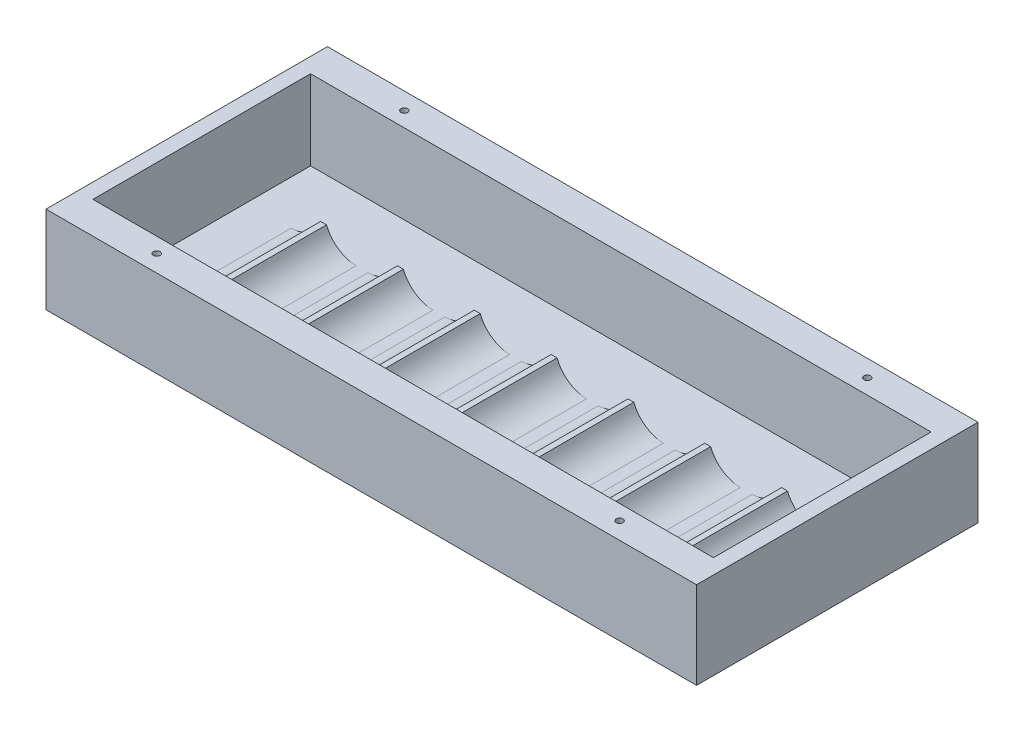
SolidWorks part; units mm, degrees
material "ABS"
ref_plane "Front Plane" through (0, 0, 0) normal (0, 0, 1) x (1, 0, 0)
ref_plane "Top Plane" through (0, 0, 0) normal (0, 1, 0) x (1, 0, 0)
ref_plane "Right Plane" through (0, 0, 0) normal (1, 0, 0) x (0, 0, -1)
sketch "Sketch1" plane through (0, 0, 0) normal (0, 1, 0) x (1, 0, 0)
  line L0 (5.08, -5.08) -> (5.08, -78.74)
  line L1 (0, 0) -> (220.16, 0)
  line L2 (0, 0) -> (0, -83.82)
  line L3 (0, -83.82) -> (220.16, -83.82)
  line L4 (220.16, 0) -> (220.16, -83.82)
  line L5 (5.08, -78.74) -> (215.08, -78.74)
  line L6 (215.08, -5.08) -> (215.08, -78.74)
  line L7 (5.08, -5.08) -> (215.08, -5.08)
  line L8 (0, 0) -> (0, 5.715)
  line L9 (0, 5.715) -> (220.16, 5.715)
  line L10 (220.16, 5.715) -> (220.16, 0)
  line L11 (0, -83.82) -> (0, -89.535)
  line L12 (0, -89.535) -> (220.16, -89.535)
  line L13 (220.16, -89.535) -> (220.16, -83.82)
  dimension "D1" = 73.66
  dimension "D2" = 210
  dimension "D4" = 10.795
  dimension "D5" = 95.25
  dimension "D3" = 5.08
extrude "Boss-Extrude1" add sketch "Sketch1" against normal blind 2.5 contours L2 L3 L4 L1
extrude "Boss-Extrude2" add sketch "Sketch1<3>" along normal blind 27 contours L10 L9 L8 L1 | L12 L13 L3 L11 | L4 L1 L2 L3 L0 L7 L6 L5 region at (110.08, 0, -2.8575) region at (110.08, 0, 2.3558) region at (110.08, 0, 86.6775)
sketch "Sketch1<3>" plane through (0, 0, 0) normal (0, 1, 0) x (1, 0, 0) same geometry as "Sketch1"
sketch "Sketch2" plane through (0, 0, 0) normal (0, 1, 0) x (-1, 0, 0)
  line L0 (-31.08, 0) -> (-31.08, 83.82) construction
  line L1 (-5.08, 5.08) -> (-5.08, 78.74) construction
  line L2 (-20.08, 0) -> (-20.08, 83.82) construction
  line L9 (0, 0) -> (-220.16, 0) construction
  line L10 (0, 83.82) -> (-220.16, 83.82) construction
  dimension "D1" = 26
  dimension "D2" = 15
sketch "Sketch5" plane through (0, 0, 5.08) normal (0, 0, 1) x (1, 0, 0)
  line L0 (31.08, 0) -> (31.08, 7) construction
  line L1 (32.08, 7) -> (30.08, 7)
  line L2 (0, 0) -> (220.16, 0) construction
  line L3 (20.08, 0) -> (42.08, 0)
  line L4 (58.08, 7) -> (56.08, 7)
  line L5 (46.08, 0) -> (68.08, 0)
  line L6 (57.08, 0) -> (57.08, 7) construction
  line L7 (84.08, 7) -> (82.08, 7)
  line L8 (72.08, 0) -> (94.08, 0)
  line L9 (83.08, 0) -> (83.08, 7) construction
  line L10 (110.08, 7) -> (108.08, 7)
  line L11 (98.08, 0) -> (120.08, 0)
  line L12 (109.08, 0) -> (109.08, 7) construction
  line L13 (136.08, 7) -> (134.08, 7)
  line L14 (124.08, 0) -> (146.08, 0)
  line L15 (135.08, 0) -> (135.08, 7) construction
  line L31 (162.08, 7) -> (160.08, 7)
  line L32 (150.08, 0) -> (172.08, 0)
  line L33 (161.08, 0) -> (161.08, 7) construction
  line L34 (188.08, 7) -> (186.08, 7)
  line L35 (176.08, 0) -> (198.08, 0)
  line L36 (187.08, 0) -> (187.08, 7) construction
  line L37 (172.6, 7) -> (170.6, 7) [skipped]
  line L38 (160.6, 0) -> (182.6, 0) [skipped]
  line L39 (171.6, 0) -> (171.6, 7) construction
  line L40 (148.18, 0) -> (148.18, 7) construction
  line L41 (137.18, 0) -> (159.18, 0) [skipped]
  line L42 (149.18, 7) -> (147.18, 7) [skipped]
  line L43 (124.76, 0) -> (124.76, 7) construction
  line L44 (113.76, 0) -> (135.76, 0) [skipped]
  line L45 (125.76, 7) -> (123.76, 7) [skipped]
  line L46 (101.34, 0) -> (101.34, 7) construction
  line L47 (90.34, 0) -> (112.34, 0) [skipped]
  line L48 (102.34, 7) -> (100.34, 7) [skipped]
  line L49 (77.92, 0) -> (77.92, 7) construction
  line L50 (66.92, 0) -> (88.92, 0) [skipped]
  line L51 (78.92, 7) -> (76.92, 7) [skipped]
  line L52 (54.5, 0) -> (54.5, 7) construction
  line L53 (43.5, 0) -> (65.5, 0) [skipped]
  line L54 (55.5, 7) -> (53.5, 7) [skipped]
  arc A0 (20.08, 0) -> (30.08, 7) centre (19.832, 10.9972) ccw
  arc A1 (42.08, 0) -> (32.08, 7) centre (42.328, 10.9972) cw
  arc A2 (68.08, 0) -> (58.08, 7) centre (68.328, 10.9972) cw
  arc A3 (46.08, 0) -> (56.08, 7) centre (45.832, 10.9972) ccw
  arc A4 (94.08, 0) -> (84.08, 7) centre (94.328, 10.9972) cw
  arc A5 (72.08, 0) -> (82.08, 7) centre (71.832, 10.9972) ccw
  arc A6 (120.08, 0) -> (110.08, 7) centre (120.328, 10.9972) cw
  arc A7 (98.08, 0) -> (108.08, 7) centre (97.832, 10.9972) ccw
  arc A8 (146.08, 0) -> (136.08, 7) centre (146.328, 10.9972) cw
  arc A9 (124.08, 0) -> (134.08, 7) centre (123.832, 10.9972) ccw
  arc A20 (172.08, 0) -> (162.08, 7) centre (172.328, 10.9972) cw
  arc A21 (150.08, 0) -> (160.08, 7) centre (149.832, 10.9972) ccw
  arc A22 (198.08, 0) -> (188.08, 7) centre (198.328, 10.9972) cw
  arc A23 (176.08, 0) -> (186.08, 7) centre (175.832, 10.9972) ccw
  arc A24 (182.6, 0) -> (172.6, 7) centre (182.848, 10.9972) cw [skipped]
  arc A25 (160.6, 0) -> (170.6, 7) centre (160.352, 10.9972) ccw [skipped]
  arc A26 (137.18, 0) -> (147.18, 7) centre (136.932, 10.9972) ccw [skipped]
  arc A27 (159.18, 0) -> (149.18, 7) centre (159.428, 10.9972) cw [skipped]
  arc A28 (113.76, 0) -> (123.76, 7) centre (113.512, 10.9972) ccw [skipped]
  arc A29 (135.76, 0) -> (125.76, 7) centre (136.008, 10.9972) cw [skipped]
  arc A30 (90.34, 0) -> (100.34, 7) centre (90.092, 10.9972) ccw [skipped]
  arc A31 (112.34, 0) -> (102.34, 7) centre (112.588, 10.9972) cw [skipped]
  arc A32 (66.92, 0) -> (76.92, 7) centre (66.672, 10.9972) ccw [skipped]
  arc A33 (88.92, 0) -> (78.92, 7) centre (89.168, 10.9972) cw [skipped]
  arc A34 (65.5, 0) -> (55.5, 7) centre (65.748, 10.9972) cw [skipped]
  arc A35 (43.5, 0) -> (53.5, 7) centre (43.252, 10.9972) ccw [skipped]
  dimension "D2" = 11
  dimension "D1" = 1
  dimension "D3" = 7
  dimension "D4" = 6
  dimension "D5" = 7
extrude "Boss-Extrude3" add sketch "Sketch5" along normal blind 32.5 from offset 21.59
extrude "Boss-Extrude4" add sketch "Sketch1<4>" against normal up to surface (2.5 mm away) contours L10 L9 L8 L1 | L12 L13 L3 L11 region at (110.08, 0, -2.8575) region at (110.08, 0, 86.6775) up to face at (110.08, -2.5, 41.91)
sketch "Sketch1<4>" plane through (0, 0, 0) normal (0, 1, 0) x (1, 0, 0) same geometry as "Sketch1"
sketch "Sketch6" plane through (0, 27, 0) normal (0, 1, 0) x (1, 0, 0)
  line L0 (0, 0) -> (220.16, 0) construction
  line L1 (220.16, 5.715) -> (220.16, -89.535) construction
  line L2 (0, -89.535) -> (0, 5.715) construction
  line L3 (0, -41.91) -> (14.6137, -41.91) construction
  point P5 (31.75, 0)
  point P6 (188.41, 0)
  point P9 (188.41, -83.82)
  point P10 (31.75, -83.82)
  dimension "D1" = 31.75
  dimension "D2" = 31.75
hole_wizard "#4-40 Tapped Hole2" positions "Sketch10" profile "Sketch9" tap size "#4-40" standard "Ansi Inch"
sketch "Sketch10" plane through (0, 27, 0) normal (0, 1, 0) x (-1, 0, 0)
  point P0 (-31.75, 0)
  point P1 (-188.41, 0)
  point P8 (-31.75, 83.82)
  point P11 (-188.41, 83.82)
sketch "Sketch9" plane through (31.75, 27, 0) normal (1, 0, 0) x (0, 0, 1)
  line L0 (0, 0) -> (0, 8.2992)
  line L1 (0, 8.2992) -> (1.1303, 7.62)
  line L2 (1.1303, 7.62) -> (1.1303, 0)
  line L5 (1.1303, 0) -> (0, 0)
  line L10 (0, 8.2992) -> (-1.1303, 7.62) construction
  line L11 (0, -6.35) -> (0, 107.95) construction
  dimension "Tap Drill Dia." = 2.2606
  dimension "Tap Drill Depth" = 7.62
  dimension "Drill Angle" = 118
cosmetic thread "Hole Thread2" parameters "D1"=5.588, "D2"=2.8448
cosmetic thread "Hole Thread3" parameters "D1"=5.588, "D2"=2.8448
cosmetic thread "Hole Thread4" parameters "D1"=5.588, "D2"=2.8448
cosmetic thread "Hole Thread5" parameters "D1"=5.588, "D2"=2.8448
sketch "Sketch12" plane through (0, 27, 0) normal (0, 1, 0) x (1, 0, 0)
  line L0 (110.08, 5.715) -> (110.08, -89.535) construction
  line L1 (0, 5.715) -> (220.16, 5.715) construction
  line L2 (0, -89.535) -> (220.16, -89.535) construction
